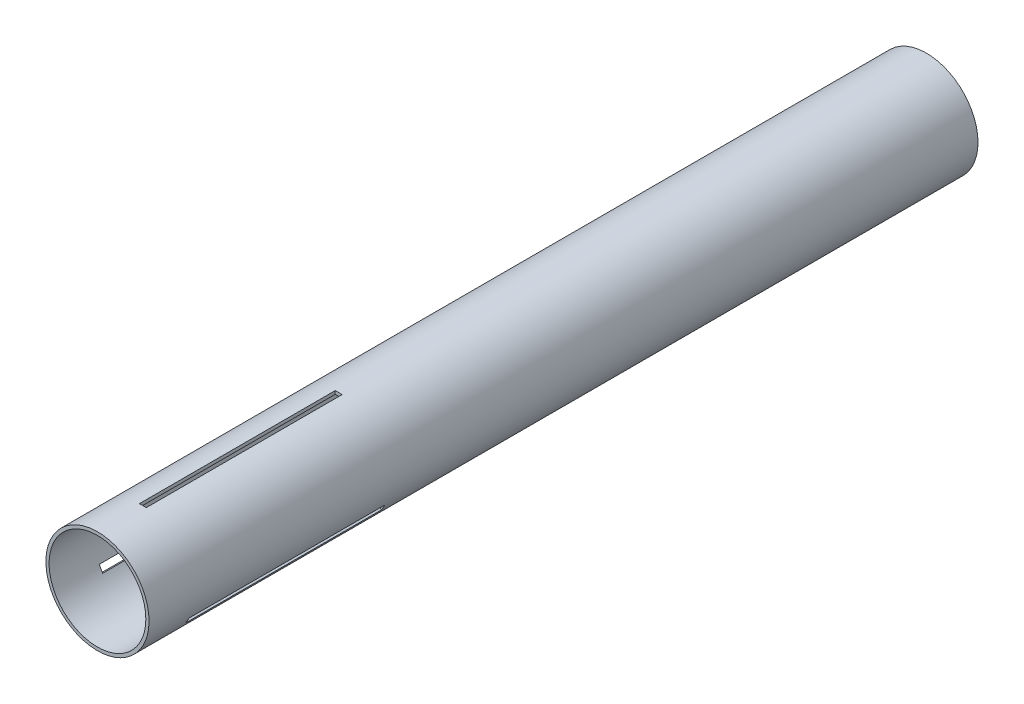
SolidWorks part; units mm, degrees
ref_plane "Front Plane" through (0, 0, 0) normal (0, 0, 1) x (1, 0, 0)
ref_plane "Top Plane" through (0, 0, 0) normal (0, 1, 0) x (1, 0, 0)
ref_plane "Right Plane" through (0, 0, 0) normal (1, 0, 0) x (0, 0, -1)
sketch "Sketch1" plane through (0, 0, 0) normal (0, 0, 1) x (1, 0, 0)
  circle A0 centre (0, 0) radius 23.6982
  circle A1 centre (0, 0) radius 22.225
extrude "Boss-Extrude1" add sketch "Sketch1" along normal blind 381
ref_plane "Plane1" through (0, 50.8, 0) normal (0, 1, 0) x (1, 0, 0)
sketch "Sketch3" plane through (0, 50.8, 0) normal (0, 1, 0) x (1, 0, 0)
  line L0 (-23.6982, -381) -> (23.6982, -381) construction
  line L2 (1.5875, -360.172) -> (1.5875, -270.172)
  line L3 (-1.5875, -360.172) -> (-1.5875, -270.172)
  line L4 (-1.5875, -270.172) -> (1.5875, -270.172)
  line L5 (-1.5875, -360.172) -> (1.5875, -360.172)
  dimension "D1" = 20.828
  dimension "D2" = 3.175
  dimension "D3" = 90
  dimension "D4" = 3.175
extrude "Cut-Extrude2" cut sketch "Sketch3" against normal up to next and the other way through all
pattern_circular "CirPattern4" count 3 over 360 about axis through (0, 0, 381) along (0, 0, 1) of "Cut-Extrude2"
ref_axis "Axis1" through (0, 0, 381) along (0, 0, -1)
sketch "Sketch4" plane through (0, 0, 270.172) normal (0, 0, 1) x (1, 0, 0)
  line L0 (-20.5232, -11.8491) -> (-19.2474, -11.1125)
  line L1 (-23.253, 0) -> (0, 0)
  arc A0 (-21.2709, -10.4477) -> (-19.6834, -13.1973) centre (0, 0) ccw construction
  arc A1 (-19.992, -9.7093) -> (-18.4045, -12.4589) centre (0, 0) ccw construction
  dimension "D1" = 30
sketch3d "3DSketch1"
  line L0 (-23.253, 0, 270.172) -> (0, 0, 270.172) construction
  line L1 (0, 0, 381) -> (0, 0, 0) construction
